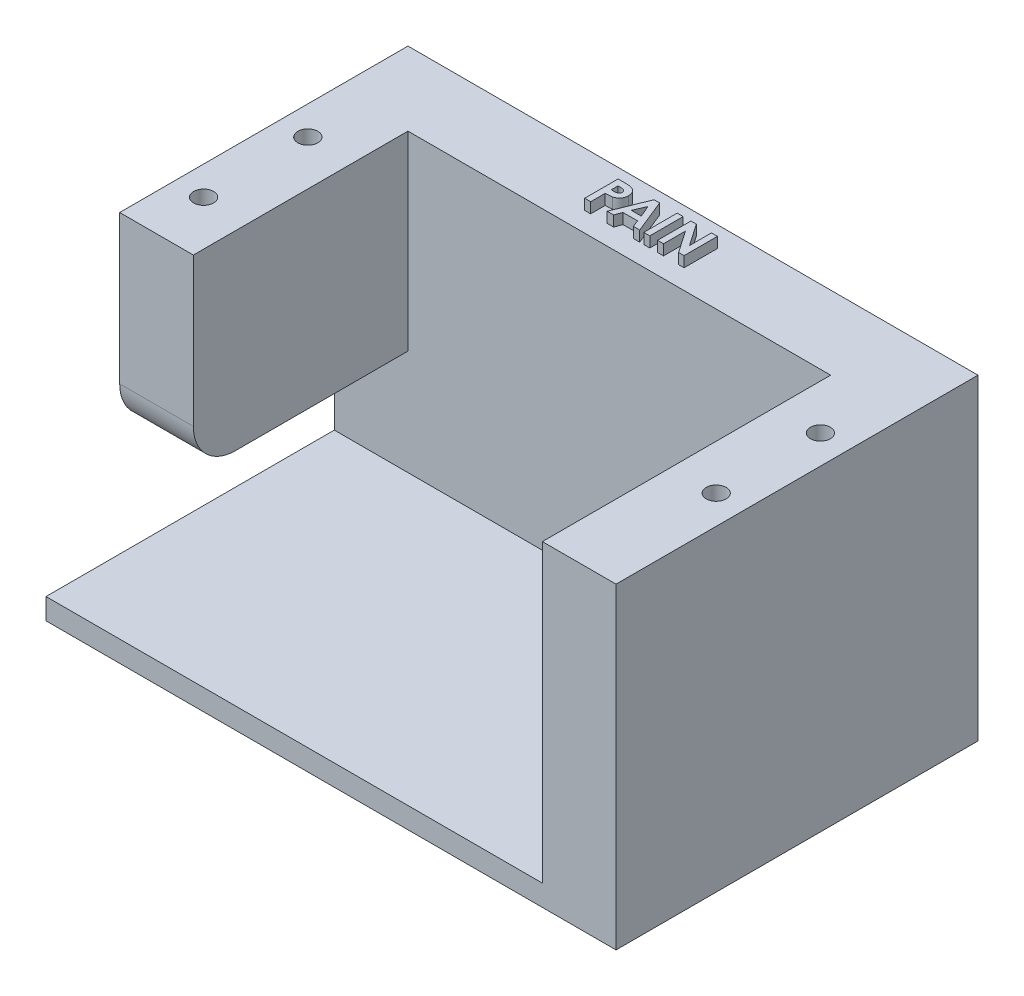
SolidWorks part; units mm, degrees
ref_plane "Front Plane" through (0, 0, 0) normal (0, 0, 1) x (1, 0, 0)
ref_plane "Top Plane" through (0, 0, 0) normal (0, 1, 0) x (1, 0, 0)
ref_plane "Right Plane" through (0, 0, 0) normal (1, 0, 0) x (0, 0, -1)
sketch "Sketch1" plane through (0, 0, 0) normal (0, 1, 0) x (1, 0, 0)
  line L0 (-27.08, -17.195) -> (27.08, -17.195)
  line L1 (-20.08, -10.195) -> (20.08, -10.195)
  line L2 (-20.08, -10.195) -> (-20.08, 10.195)
  line L3 (-20.08, 10.195) -> (20.08, 10.195)
  line L4 (20.08, -10.195) -> (20.08, 10.195)
  line L5 (-20.08, -10.195) -> (20.08, 10.195) construction
  line L6 (-20.08, 10.195) -> (20.08, -10.195) construction
  line L7 (27.08, -17.195) -> (27.08, 17.195)
  line L8 (-27.08, 17.195) -> (27.08, 17.195)
  line L9 (-27.08, -17.195) -> (-27.08, 17.195)
  point P0 (0, 0)
  dimension "D1" = 40.16
  dimension "D2" = 20.39
  dimension "D3" = 7
extrude "Boss-Extrude1" add sketch "Sketch1" along normal blind 2 contours L1 L4 L3 L2 | L9 L0 L7 L8 L4 L1 L2 L3 region at (-26.4384, 0, 0) region at (0, 0, 0)
sketch "Sketch2" plane through (0, 2, 0) normal (0, 1, 0) x (1, 0, 0)
  line L4 (-20.08, -10.195) -> (20.08, -10.195)
  line L5 (20.08, -10.195) -> (20.08, 10.195)
  line L6 (20.08, 10.195) -> (-20.08, 10.195)
  line L7 (-20.08, 10.195) -> (-20.08, -10.195)
  line L8 (-20.08, -10.195) -> (20.08, -10.195)
  line L9 (20.08, -10.195) -> (20.08, 10.195)
  line L10 (20.08, 10.195) -> (-20.08, 10.195)
  line L11 (-20.08, 10.195) -> (-20.08, -10.195)
  line L12 (-27.08, -17.195) -> (27.08, -17.195)
  line L13 (27.08, -17.195) -> (27.08, 17.195)
  line L14 (27.08, 17.195) -> (-27.08, 17.195)
  line L15 (-27.08, 17.195) -> (-27.08, -17.195)
  line L16 (-27.08, -17.195) -> (27.08, -17.195) construction
  line L17 (27.08, -17.195) -> (27.08, 17.195) construction
  line L18 (27.08, 17.195) -> (-27.08, 17.195) construction
  line L19 (-27.08, 17.195) -> (-27.08, -17.195) construction
  line M9 (-27.08, 17.195) -> (-27.08, -17.195)
  line M10 (-27.08, -17.195) -> (27.08, -17.195)
  line M11 (27.08, -17.195) -> (27.08, 17.195)
  line M12 (27.08, 17.195) -> (-27.08, 17.195)
  dimension "D1" = 0
  dimension "D2" = 0
extrude "Boss-Extrude2" add sketch "Sketch2" along normal blind 28.1 contours L11 L10 L9 L8 M12 M9 M10 M11 region at (-26.4384, 2, 0)
sketch "Sketch3" plane through (0, 30.1, 0) normal (0, 1, 0) x (1, 0, 0)
  line L1 (20.08, -10.195) -> (-27.08, -10.195)
  line L2 (20.08, -10.195) -> (20.08, -17.195)
  line L3 (20.08, -17.195) -> (-27.08, -17.195)
  line L4 (-27.08, -10.195) -> (-27.08, -17.195)
extrude "Cut-Extrude1" cut sketch "Sketch3" against normal up to surface (28.1 mm away) up to face at (0, 2, 0)
sketch "Sketch5" plane through (-20.08, 0, 0) normal (1, 0, 0) x (0, 0, -1)
  line L0 (-10.195, 30.1) -> (-10.195, 2) construction
  line L1 (10.195, 2) -> (-10.195, 2)
  line L2 (10.195, 2) -> (10.195, 12)
  line L3 (10.195, 12) -> (-10.195, 12)
  line L4 (-10.195, 2) -> (-10.195, 12)
  dimension "D1" = 10
extrude "Cut-Extrude2" cut sketch "Sketch5" against normal up to next
fillet "Fillet1" radius 4 1 edges at (-23.58, 12, 10.195)
sketch "Sketch6" plane through (0, 30.1, 0) normal (0, 1, 0) x (1, 0, 0)
  line L0 (-1.9157, 0) -> (18.1643, 0) construction
  line L2 (0, 0) -> (0, 10.195) construction
  circle A0 centre (-24.35, -4.95) radius 2.25 construction
  circle A1 centre (-24.35, -4.95) radius 0.95
  circle A2 centre (-24.35, 4.95) radius 0.95
  circle A3 centre (24.35, 4.95) radius 0.95
  circle A4 centre (24.35, -4.95) radius 0.95
  dimension "D1" = 2.7
  dimension "D2" = 22.1
  dimension "D3" = 4.5
  dimension "D4" = 1.9
extrude "Cut-Extrude3" cut sketch "Sketch6" against normal blind 12
sketch "Sketch7" plane through (0, 30.1, 0) normal (0, 1, 0) x (1, 0, 0)
  text T0 "<b>PAIN</b>" font "Century Gothic" height 3.175
extrude "Boss-Extrude3" add sketch "Sketch7" along normal blind 1
